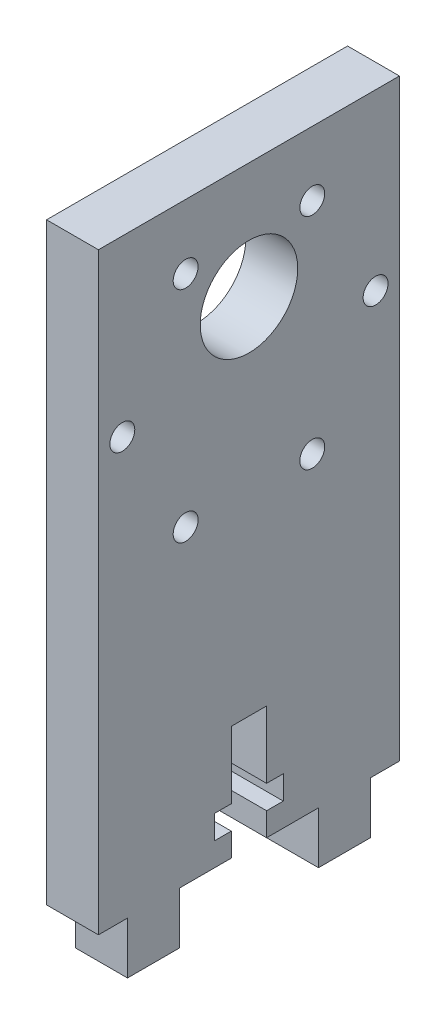
SolidWorks part; units mm, degrees
ref_plane "Front Plane" through (0, 0, 0) normal (0, 0, 1) x (1, 0, 0)
ref_plane "Top Plane" through (0, 0, 0) normal (0, 1, 0) x (1, 0, 0)
ref_plane "Right Plane" through (0, 0, 0) normal (1, 0, 0) x (0, 0, -1)
sketch "Motor plate" plane through (0, 0, 0) normal (1, 0, 0) x (0, 0, -1)
  line L0 (0, 15.0079) -> (7.747, 28.4261) construction
  line L1 (-18.415, -36.3001) -> (-14.859, -36.3001)
  line L2 (-18.415, -36.3001) -> (-18.415, 36.3001)
  line L3 (-18.415, 36.3001) -> (18.415, 36.3001)
  line L4 (18.415, -36.3001) -> (18.415, 36.3001)
  line L5 (-18.415, -36.3001) -> (18.415, 36.3001) construction
  line L6 (-18.415, 36.3001) -> (18.415, -36.3001) construction
  line L7 (14.859, -36.3001) -> (18.415, -36.3001)
  line L13 (0, 36.3001) -> (0, -24.5526) construction
  circle A0 centre (7.747, 28.4261) radius 1.524
  circle A1 centre (15.494, 15.0079) radius 1.524
  circle A2 centre (7.747, 1.5897) radius 1.524
  circle A3 centre (-7.747, 1.5897) radius 1.524
  circle A4 centre (-15.494, 15.0079) radius 1.524
  circle A5 centre (-7.747, 28.4261) radius 1.524
  circle A6 centre (0, 22.1199) radius 5.969
  circle A7 centre (0, 15.0079) radius 18.415 construction
  point P0 (0, 0)
  point P13 (0, -3.4071)
  point P15 (0, 15.0079)
  point P32 (0, 15.0079)
  line B0 (-8.509, -36.3001) -> (-8.509, -42.6501)
  line B1 (-8.509, -42.6501) -> (-14.859, -42.6501)
  line B2 (-14.859, -42.6501) -> (-14.859, -36.3001)
  line B3 (-2.159, -36.3001) -> (-2.159, -33.4324)
  line B4 (-2.159, -33.4324) -> (-4.2, -33.4324)
  line B5 (-4.2, -33.4324) -> (-4.2, -30.5324)
  line B6 (-4.2, -30.5324) -> (-2.159, -30.5324)
  line B7 (-2.159, -30.5324) -> (-2.159, -22.3301)
  line B8 (-2.159, -22.3301) -> (2.159, -22.3301)
  line B9 (2.159, -22.3301) -> (2.159, -30.5324)
  line B10 (2.159, -30.5324) -> (4.2, -30.5324)
  line B11 (4.2, -30.5324) -> (4.2, -33.4324)
  line B12 (4.2, -33.4324) -> (2.159, -33.4324)
  line B13 (2.159, -33.4324) -> (2.159, -36.3001)
  line B14 (0, -22.3301) -> (0, -36.3001) construction
  line B15 (8.509, -36.3001) -> (2.159, -36.3001)
  line B16 (14.859, -42.6501) -> (14.859, -36.3001)
  line B17 (-8.509, -36.3001) -> (-2.159, -36.3001)
  line B18 (8.509, -42.6501) -> (14.859, -42.6501)
  line B19 (8.509, -36.3001) -> (8.509, -42.6501)
  dimension "D3" = 30
  dimension "D4" = 15.494
  dimension "D5" = 3.048
  dimension "D8" = 11.938
  dimension "D2" = 36.83
  dimension "D1" = 58.42
  dimension "D6" = 6.35
  dimension "D7" = 6
  dimension "D9" = 7.112
sketch_block_instance "Male T-slot assembly-1"
sketch_block "Male T-slot assembly" parameters "D1"=6.35, "D2"=6.35, "D3"=4.318, "D4"=2.9, "D5"=8.4, "D6"=13.97, "D7"=6.35
extrude "Boss-Extrude1" add sketch "Motor plate" along normal blind 6.35 contours L3 | L4 L3 L2 A6 A5 A4 A3 A2 A1 A0 region at (0, -1.6502, 0)
equation "\"Ball Diameter\"= 1.75in"
equation "\"Sheet Thickness\"= 0.25in"
equation "\"Screw Diameter\"= .17in"
equation "\"Robot Diameter\"= 14in"
equation "\"Castor Screw Diameter\"= 0.22in"
equation "\"Wheel Diameter\" = 4in"
equation "\"Nut Diameter\" = 8.4mm"
equation "\"Nut Height\" = 2.9mm"
equation "\"Screw Height\" = 0.55in"
equation "\"D1@Boss-Extrude1\"=\"Sheet Thickness\""
equation "\"Ball Radius\" = \"Ball Diameter\"/2"
equation "\"Pulley Diameter\" = 1in"
equation "\"Reactor Height\" = 14in"
equation "\"Elevator Height\" = 11.5in"
equation "\"Elevator Width\" = \"Ball Diameter\" + 0.25in"
equation "\"Elevator Bearing Diameter\" = sqr(2*(\"Sheet Thickness\"^2)) + 0.2in"
equation "\"Elevator Axle Endcap Diameter\" = \"Pulley Diameter\" + 0.25in"
equation "\"Elevator Axle Length\" = \"Elevator Width\" + 8*\"Sheet Thickness\""
equation "\"Elevator Clearance from Axis\" = 3.28in"
equation "\"Elevator Horizontal Clearance\" = \"Elevator Width\" + 0.5in"
equation "\"Claw Horizontal Seperation\" = (\"Elevator Width\"/2) - (1.5 * \"Sheet Thickness\") - 0.15in"
equation "\"Claw Radius\" = \"Ball Radius\" + 0.1in"
equation "\"Castor Wheel Height\" = 1.25in"
